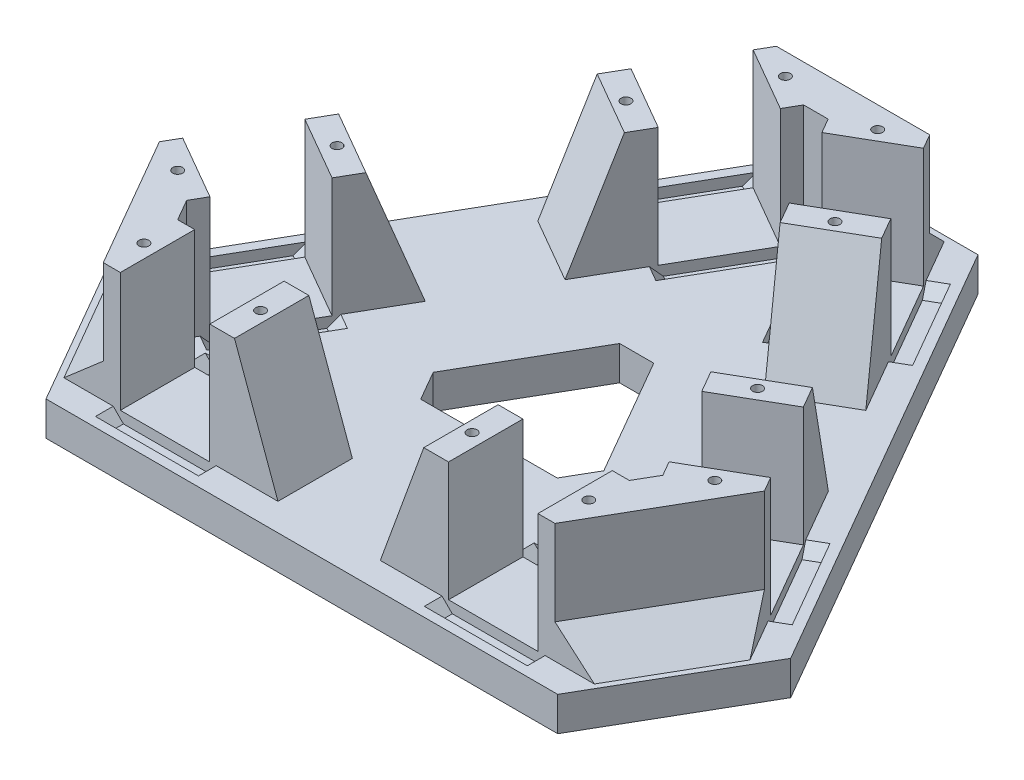
SolidWorks part; units mm, degrees
ref_plane "Front Plane" through (0, 0, 0) normal (0, 0, 1) x (1, 0, 0)
ref_plane "Top Plane" through (0, 0, 0) normal (0, 1, 0) x (1, 0, 0)
ref_plane "Right Plane" through (0, 0, 0) normal (1, 0, 0) x (0, 0, -1)
sketch "Sketch1" plane through (0, 0, 0) normal (0, 1, 0) x (1, 0, 0)
  line L1 (0, 144.3376) -> (-125, -72.1688)
  line L2 (-125, -72.1688) -> (125, -72.1688)
  line L3 (125, -72.1688) -> (0, 144.3376)
  circle A0 centre (0, 0) radius 72.1688 construction
  dimension "D1" = 250
extrude "Boss-Extrude1" add sketch "Sketch1" along normal blind 10
ref_axis "Axis1" through (0, 47.25, 0) along (0, -1, 0)
sketch "Sketch2" plane through (0, 10, 0) normal (0, 1, 0) x (1, 0, 0)
  line L0 (-125, -72.1688) -> (125, -72.1688) construction
  line L1 (30, -42.3688) -> (35, -42.3688)
  line L2 (30, -42.3688) -> (30, -64.1688)
  line L3 (30, -64.1688) -> (35, -64.1688)
  line L4 (35, -42.3688) -> (35, -64.1688)
  line L5 (61.2, -42.3688) -> (66.2, -42.3688)
  line L6 (61.2, -42.3688) -> (61.2, -64.1688)
  line L7 (61.2, -64.1688) -> (66.2, -64.1688)
  line L8 (66.2, -42.3688) -> (66.2, -64.1688)
  line L9 (0, 0) -> (0, -115.0125) construction
  line L10 (-66.2, -42.3688) -> (-66.2, -64.1688)
  line L11 (-61.2, -64.1688) -> (-66.2, -64.1688)
  line L12 (-61.2, -42.3688) -> (-61.2, -64.1688)
  line L13 (-61.2, -42.3688) -> (-66.2, -42.3688)
  line L14 (-35, -42.3688) -> (-35, -64.1688)
  line L15 (-30, -64.1688) -> (-35, -64.1688)
  line L16 (-30, -42.3688) -> (-30, -64.1688)
  line L17 (-30, -42.3688) -> (-35, -42.3688)
  dimension "D1" = 21.8
  dimension "D2" = 21.8
  dimension "D3" = 26.2
  dimension "D4" = 5
  dimension "D5" = 5
  dimension "D6" = 8
  dimension "D7" = 30
extrude "Boss-Extrude2" add sketch "Sketch2" along normal blind 35
pattern_circular "CirPattern1" count 3 over 360 about axis through (0, 47.25, 0) along (0, -1, 0) of "Boss-Extrude2"
chamfer "Chamfer1" distance 50 angle 60 3 edges at (125, 5, 72.1688) (0, 5, -144.3376) (-125, 5, 72.1688) first distance on face at (0, 5, 72.1688) first distance on face at (-62.5, 5, -36.0844)
sketch "Sketch3" plane through (0, 45, 0) normal (0, 1, 0) x (1, 0, 0)
  line L0 (69.7924, -36.1465) -> (66.2, -42.3688)
  line L1 (66.2, -42.3688) -> (66.2, -64.1688)
  line L2 (66.2, -64.1688) -> (88.6718, -25.2465)
  line L3 (88.6718, -25.2465) -> (69.7924, -36.1465)
extrude "Boss-Extrude3" add sketch "Sketch3" against normal up to surface (35 mm away) up to face at (0, 10, 0)
pattern_circular "CirPattern2" count 3 over 360 about axis through (0, 47.25, 0) along (0, -1, 0) of "Boss-Extrude3"
chamfer "Chamfer2" distance 10 angle 45 3 edges at (-77.4359, 10, 44.7076) (0, 10, -89.4153) (77.4359, 10, 44.7076)
chamfer "Chamfer3" distance 15 angle 70 6 edges at (-30, 10, 53.2688) (-31.1321, 10, -52.6152) (-61.1321, 10, -0.6536) (30, 10, 53.2688) (61.1321, 10, -0.6536) (31.1321, 10, -52.6152) first distance on face at (0, 10, -84.3002)
sketch "Sketch4" plane through (0, 10, 0) normal (0, 1, 0) x (1, 0, 0)
  line L1 (0, 34.641) -> (-30, -17.3205)
  line L2 (-30, -17.3205) -> (30, -17.3205)
  line L3 (30, -17.3205) -> (0, 34.641)
  circle A0 centre (0, 0) radius 17.3205 construction
  dimension "D1" = 60
extrude "Cut-Extrude1" cut sketch "Sketch4" against normal blind 35
chamfer "Chamfer4" distance 10 angle 60 3 edges at (-30, 5, 17.3205) (30, 5, 17.3205) (0, 5, -34.641) first distance on face at (0, 5, 17.3205) first distance on face at (15, 5, -8.6603)
sketch "Sketch6" plane through (0, 10, 0) normal (0, 1, 0) x (1, 0, 0)
  line L0 (0, 0) -> (0, -27.756) construction
  line L1 (27.739, -53.2688) -> (61.2, -53.2688) construction
  line L2 (27.739, -42.3688) -> (27.739, -64.1688) construction
  line L3 (61.2, -42.3688) -> (61.2, -64.1688) construction
  line L4 (35, -42.3688) -> (27.739, -42.3688) construction
  line L5 (32.1, -42.3688) -> (64.3, -42.3688)
  line L6 (32.1, -42.3688) -> (32.1, -37.1688)
  line L7 (32.1, -37.1688) -> (64.3, -37.1688)
  line L8 (64.3, -42.3688) -> (64.3, -37.1688)
  line L9 (60.8, -37.3688) -> (63.2, -37.3688) construction
  line L10 (66.2, -42.3688) -> (61.2, -42.3688) construction
  line L11 (64.2, -38.3688) -> (64.2, -42.3688) construction
  line L12 (32.2, -38.3688) -> (32.2, -42.3688) construction
  line L13 (64.3, -64.1688) -> (64.3, -69.3688)
  line L14 (32.1, -69.3688) -> (64.3, -69.3688)
  line L15 (32.1, -64.1688) -> (32.1, -69.3688)
  line L16 (32.1, -64.1688) -> (64.3, -64.1688)
  line L17 (-27.739, -53.2688) -> (-61.2, -53.2688) construction
  line L18 (-32.1, -64.1688) -> (-64.3, -64.1688)
  line L19 (-32.1, -64.1688) -> (-32.1, -69.3688)
  line L20 (-32.1, -69.3688) -> (-64.3, -69.3688)
  line L21 (-64.3, -64.1688) -> (-64.3, -69.3688)
  line L22 (-64.3, -42.3688) -> (-64.3, -37.1688)
  line L23 (-32.1, -37.1688) -> (-64.3, -37.1688)
  line L24 (-32.1, -42.3688) -> (-32.1, -37.1688)
  line L25 (-32.1, -42.3688) -> (-64.3, -42.3688)
  dimension "D1" = 0.2
  dimension "D2" = 0.1
  dimension "D3" = 0.1
extrude "Cut-Extrude2" cut sketch "Sketch6" against normal blind 3
pattern_circular "CirPattern5" count 3 over 360 about axis through (0, 47.25, 0) along (0, -1, 0) of "Cut-Extrude2"
chamfer "Chamfer6" distance 4 angle 45 8 edges at (-89.9735, 7, 22.301) (-73.8735, 7, -5.585) (-50.4908, 7, 7.915) (-64.3, 7, 66.7688) (-32.1, 7, 66.7688) (-32.1, 7, 39.7688) (-66.5908, 7, 35.801) (-64.3, 7, 39.7688)
chamfer "Chamfer7" distance 4 angle 45 8 edges at (73.8735, 7, -5.585) (89.9735, 7, 22.301) (32.1, 7, 39.7688) (50.4908, 7, 7.915) (66.5908, 7, 35.801) (64.3, 7, 39.7688) (64.3, 7, 66.7688) (32.1, 7, 66.7688)
chamfer "Chamfer8" distance 4 angle 45 8 edges at (-25.6735, 7, -89.0698) (41.7735, 7, -61.1838) (18.3908, 7, -47.6838) (-41.7735, 7, -61.1838) (-18.3908, 7, -47.6838) (-2.2908, 7, -75.5698) (2.2908, 7, -75.5698) (25.6735, 7, -89.0698)
sketch "Sketch7" plane through (0, 45, 0) normal (0, 1, 0) x (1, 0, 0)
  line L0 (35, -53.2688) -> (31, -53.2688) construction
  line L1 (35, -64.1688) -> (35, -42.3688) construction
  line L2 (61.2, -53.2688) -> (65.2, -53.2688) construction
  line L3 (61.2, -42.3688) -> (61.2, -64.1688) construction
  line L4 (76.7321, -26.3664) -> (78.7321, -29.8305) construction
  line L5 (86.1718, -20.9164) -> (67.2924, -31.8164) construction
  line L6 (63.6321, -3.6765) -> (61.6321, -0.2124) construction
  line L7 (54.1924, -9.1265) -> (73.0718, 1.7735) construction
  circle A0 centre (31, -53.2688) radius 1.45
  circle A1 centre (65.2, -53.2688) radius 1.45
  circle A2 centre (78.7321, -29.8305) radius 1.45
  circle A3 centre (61.6321, -0.2124) radius 1.45
  dimension "D5" = 2.9
  dimension "D6" = 2.9
  dimension "D7" = 2.9
  dimension "D8" = 2.9
  dimension "D1" = 4
  dimension "D2" = 4
  dimension "D3" = 4
  dimension "D4" = 4
extrude "Cut-Extrude3" cut sketch "Sketch7" against normal blind 12
pattern_circular "CirPattern7" count 3 over 360 about axis through (0, 47.25, 0) along (0, -1, 0) of "Cut-Extrude3"
